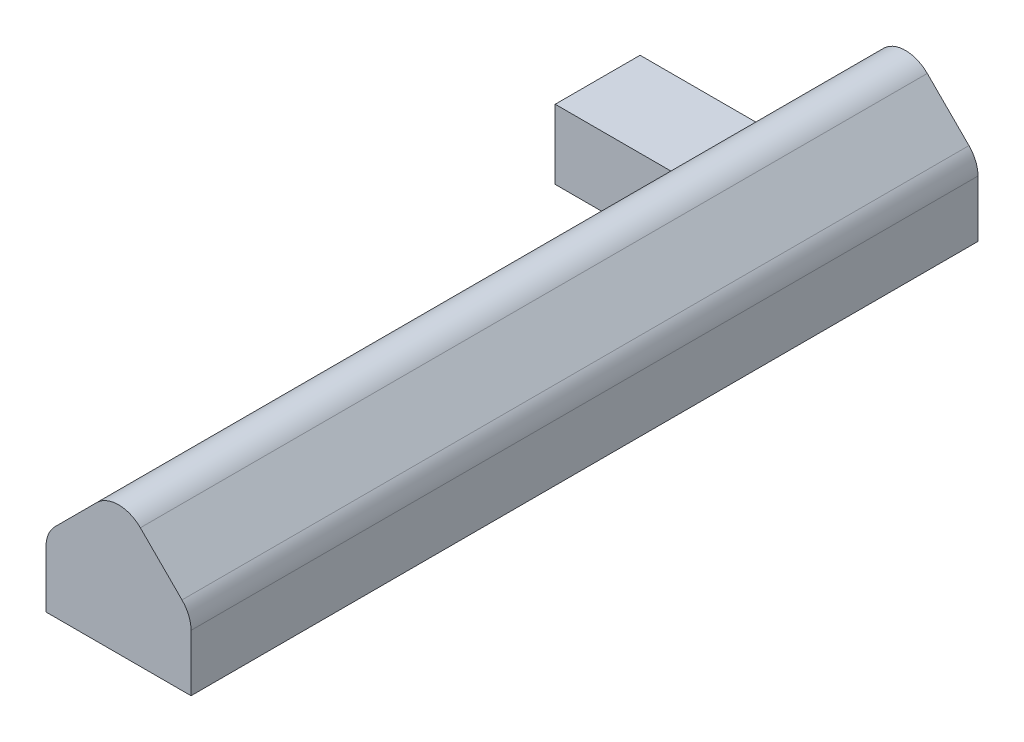
SolidWorks part; units mm, degrees
ref_plane "Płaszczyzna przednia" through (0, 0, 0) normal (0, 0, 1) x (1, 0, 0)
ref_plane "Płaszczyzna górna" through (0, 0, 0) normal (0, 1, 0) x (1, 0, 0)
ref_plane "Płaszczyzna prawa" through (0, 0, 0) normal (1, 0, 0) x (0, 0, -1)
sketch "Szkic1" plane through (0, 0, 0) normal (0, 0, 1) x (1, 0, 0)
  line L0 (0, 0) -> (0, 9.4056) construction
  line L1 (-4.7, 2.25) -> (4.7, 2.25)
  line L2 (-4.7, 2.25) -> (-4.7, -2.25)
  line L3 (-4.7, -2.25) -> (4.7, -2.25)
  line L4 (4.7, 2.25) -> (4.7, -2.25)
  line L5 (-4.7, 2.25) -> (4.7, -2.25) construction
  line L6 (-4.7, -2.25) -> (4.7, 2.25) construction
  line L7 (-4.7, 2.25) -> (0, 6.95)
  line L8 (0, 6.95) -> (4.7, 2.25)
  point P0 (0, 0)
  dimension "D1" = 9.4
  dimension "D2" = 4.5
  dimension "D3" = 45
extrude "Dodanie-wyciągnięcie1" add sketch "Szkic1" along normal blind 51 contours L8 L7 L1 | L4 L1 L2 L3 region at (0, 3.8167, 0) region at (0, 0, 0)
sketch "Szkic2" plane through (0, -2.25, 0) normal (0, -1, 0) x (1, 0, 0)
  line L0 (0, 0) -> (0, 51) construction
  line L1 (-4.7, 0) -> (4.7, 0) construction
  line L2 (-4.7, 51) -> (4.7, 51) construction
  line L3 (4.7, 51) -> (4.7, 0) construction
  line L8 (-10, 25) -> (-10, 41)
  line L9 (0, 41) -> (-10, 41)
  line L10 (0, 25) -> (0, 41)
  line L11 (0, 25) -> (-10, 25)
  line L12 (-2, 41) -> (-2, 25)
  line M6 (4.7, 0) -> (4.7, 51)
  line M8 (-4.7, 51) -> (-4.7, 0)
  dimension "D1" = 6.7
  dimension "D2" = 14.7
  dimension "D3" = 25
  dimension "D4" = 41
extrude "Wytnij-wyciągnięcie1" cut sketch "Szkic2" against normal blind 10 contours M6 | L12 L9 L11 M8 region at (-3.35, -2.25, 33)
ref_plane "Płaszczyzna1" through (-22.5, 11.75, 5) normal (0, -1, 0) x (-1, 0, 0)
sketch "Szkic4" plane through (0, -2.25, 0) normal (0, -1, 0) x (1, 0, 0)
  line L0 (0, 0) -> (0, 5) construction
  line L2 (-4.7, 0) -> (4.7, 0) construction
  line L3 (0, 0) -> (0, -7.3747) construction
  line L9 (7.5, -5) -> (-7.5, -5)
  line L10 (7.5, -5) -> (7.5, 5)
  line L11 (7.5, 5) -> (-7.5, 5)
  line L12 (-7.5, -5) -> (-7.5, 5)
  line L13 (7.5, -5) -> (-7.5, 5) construction
  line L14 (7.5, 5) -> (-7.5, -5) construction
  line L15 (13.1781, -10) -> (-13.1781, -10)
  line L16 (13.1781, -10) -> (13.1781, -5)
  line L17 (13.1781, -5) -> (-13.1781, -5)
  line L18 (-13.1781, -10) -> (-13.1781, -5)
  line L19 (13.1781, -10) -> (-13.1781, -5) construction
  line L20 (13.1781, -5) -> (-13.1781, -10) construction
  point P4 (0, 0)
  point P10 (0, -7.5)
  dimension "D1" = 5
  dimension "D2" = 15
  dimension "D3" = 10
  dimension "D4" = 5
fillet "Zaokrąglenie1" radius 2 3 edges at (4.7, 2.25, 25.5) (-4.7, 2.25, 46) (0, 6.95, 25.5)
sketch "Szkic5" plane through (0, -2.25, 0) normal (0, -1, 0) x (1, 0, 0)
  line L0 (-4.7, 51) -> (-4.7, 41) construction
  line L1 (-4.7, 5) -> (-12.2, 5)
  line L2 (-4.7, 5) -> (-4.7, 10.5)
  line L3 (-4.7, 10.5) -> (-12.2, 10.5)
  line L4 (-12.2, 5) -> (-12.2, 10.5)
  line L5 (-8.45, 10.5) -> (-8.45, 5) construction
  line L6 (-4.7, 7.75) -> (-12.2, 7.75) construction
  line L7 (-4.7, 0) -> (4.7, 0) construction
  line L8 (-4.7, 51) -> (-4.7, 41) construction
  point P196 (-8.45, 7.75)
  dimension "D1" = 5.5
  dimension "D2" = 7.5
  dimension "D3" = 5
extrude "Dodanie-wyciągnięcie4" add sketch "Szkic5" against normal up to vertex (4.5 mm away) up to point (-4.7, 2.25, 25)
